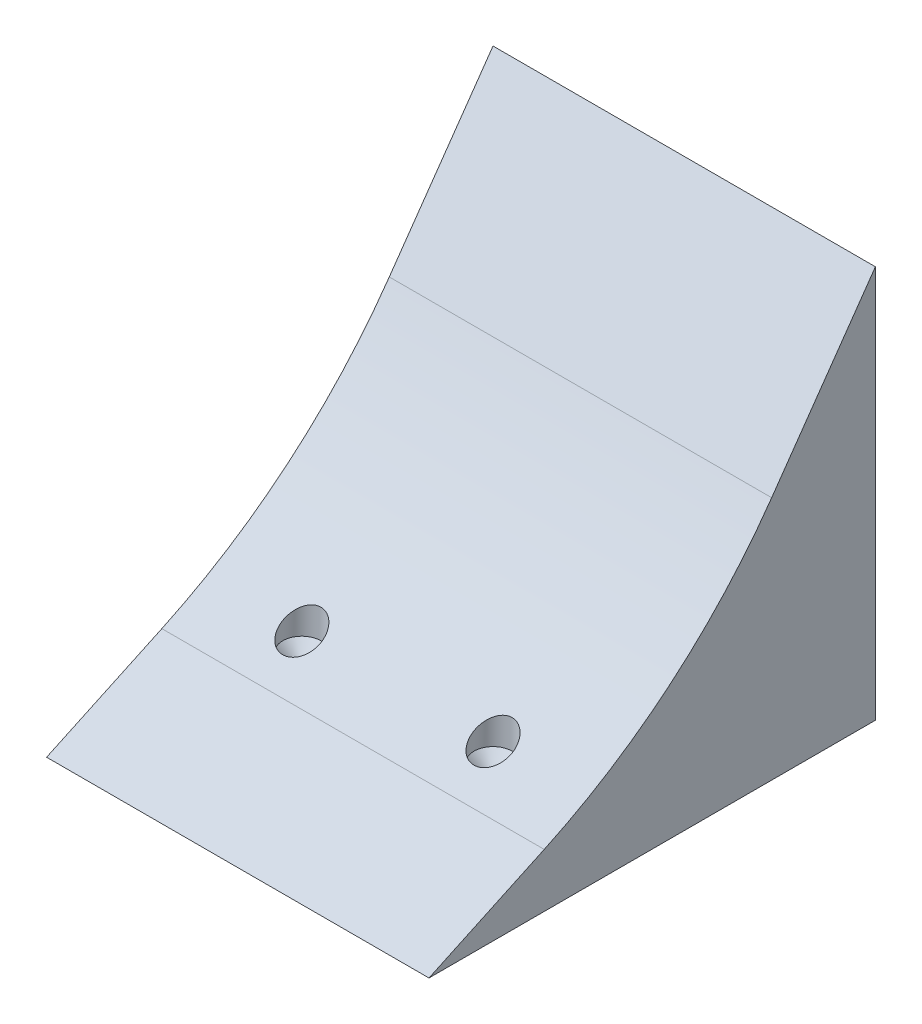
SolidWorks part; units mm, degrees
ref_plane "Front Plane" through (0, 0, 0) normal (0, 0, 1) x (1, 0, 0)
ref_plane "Top Plane" through (0, 0, 0) normal (0, 1, 0) x (1, 0, 0)
ref_plane "Right Plane" through (0, 0, 0) normal (1, 0, 0) x (0, 0, -1)
sketch "Sketch1" plane through (0, 0, 0) normal (1, 0, 0) x (0, 0, -1)
  line L0 (-61.4896, -124.3152) -> (57.1241, -124.3152)
  line L1 (57.1241, -124.3152) -> (57.1241, -19.9667)
  line L2 (29.5629, -59.3282) -> (57.1241, -19.9667)
  line L3 (-30.8689, -110.0365) -> (-61.4896, -124.3152)
  arc A0 (-30.8689, -110.0365) -> (29.5629, -59.3282) centre (-95.2759, 28.0848) ccw
  dimension "D2" = 152.4
  dimension "D1" = 55
  dimension "D3" = 25
extrude "Boss-Extrude1" add sketch "Sketch1" along normal blind 101.6
sketch "Sketch2" plane through (0, -124.3152, 0) normal (0, -1, 0) x (1, 0, 0)
  line L0 (25.4, 19.0759) -> (97.5645, 19.0759) construction
  line L1 (0, 61.4896) -> (0, -57.1241) construction
  line L2 (101.6, -57.1241) -> (0, -57.1241) construction
  circle A0 centre (25.4, 19.0759) radius 1.905
  circle A1 centre (76.2, 19.0759) radius 1.905
  dimension "D3" = 3.81
  dimension "D4" = 3.81
  dimension "D1" = 50.8
  dimension "D2" = 25.4
  dimension "D5" = 76.2
extrude "Cut-Extrude1" cut sketch "Sketch2" against normal blind 101.6
sketch "Sketch3" plane through (0, -124.3152, 0) normal (0, -1, 0) x (1, 0, 0)
  circle A0 centre (25.4, 19.0759) radius 5.08
  circle A1 centre (76.2, 19.0759) radius 5.08
  dimension "D1" = 10.16
  dimension "D2" = 10.16
extrude "Cut-Extrude2" cut sketch "Sketch3" against normal blind 101.6 from offset 12.7 offset against normal yes
chamfer "Chamfer1" distance 3.048 angle 45 2 edges at (76.2, -111.6152, 13.9959) (25.4, -111.6152, 13.9959)
